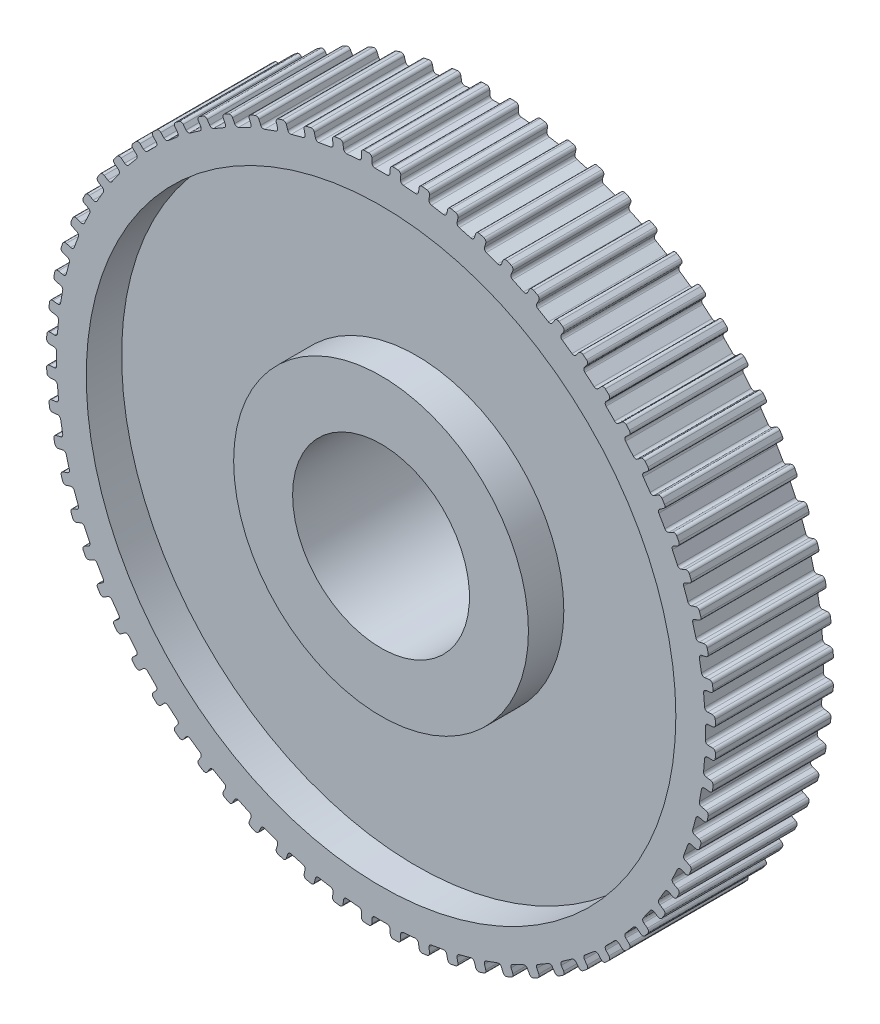
SolidWorks part; units mm, degrees
ref_plane "Front Plane" through (0, 0, 0) normal (0, 0, 1) x (1, 0, 0)
ref_plane "Top Plane" through (0, 0, 0) normal (0, 1, 0) x (1, 0, 0)
ref_plane "Right Plane" through (0, 0, 0) normal (1, 0, 0) x (0, 0, -1)
sketch "Sketch1" plane through (0, 0, 0) normal (0, 0, 1) x (1, 0, 0)
  circle A0 centre (0, 0) radius 56.75
  circle A1 centre (0, 0) radius 3.5
  dimension "D1" = 113.5
  dimension "D2" = 7
extrude "Boss-Extrude1" add sketch "Sketch1" along normal blind 20
ref_plane "Plane4" through (0, 0, 20) normal (0, 0, 1) x (1, 0, 0)
sketch "Sketch3" plane through (0, 0, 20) normal (0, 0, 1) x (1, 0, 0)
  circle A0 centre (0, 0) radius 25
  circle A3 centre (0, 0) radius 50
  dimension "D1" = 50
  dimension "D2" = 100
extrude "Cut-Extrude1" cut sketch "Sketch3" against normal blind 6
ref_plane "Plane5" through (0, 0, 10) normal (0, 0, 1) x (1, 0, 0)
mirror "Mirror1" about plane through (0, 0, 10) normal (0, 0, 1) of "Cut-Extrude1"
sketch "Sketch5" plane through (0, 0, 0) normal (0, 0, -1) x (-1, 0, 0)
  circle A1 centre (0, 0) radius 25 construction
  circle A2 centre (0, 0) radius 25
extrude "Boss-Extrude2" add sketch "Sketch5" along normal blind 10
sketch "Sketch6" plane through (0, 0, 0) normal (0, 0, -1) x (-1, 0, 0)
  line L0 (56.75, 0) -> (57.25, 0) construction
  line L1 (55, 1.5) -> (55, -1.5)
  line L2 (55, -1.5) -> (56.966, -1.6)
  line L3 (56.966, -1.6) -> (57, 0)
  line L4 (56.966, 1.6) -> (57, 0)
  line L5 (55, 1.5) -> (56.966, 1.6)
  circle A0 centre (0, 0) radius 56.75 construction
  point P12 (55, 0)
  dimension "D1" = 1.5
  dimension "D2" = 2
  dimension "D3" = 55
  dimension "D4" = 1.6
extrude "Cut-Extrude2" cut sketch "Sketch6" against normal through all
fillet "Fillet1" radius 0.5 2 edges at (-56.7278, -1.5879, 10) (-56.7278, 1.5879, 10)
fillet "Fillet3" radius 0.5 2 edges at (-55, -1.5, 10) (-55, 1.5, 10)
pattern_circular "CirPattern1" count 72 over 360 about axis through (0, 0, 0) along (0, 0, 1) of "Cut-Extrude2", "Fillet1", "Fillet3"
sketch "Sketch7" plane through (0, 0, 0) normal (0, 0, 1) x (1, 0, 0)
  circle A0 centre (0, 0) radius 3.5 construction
  circle A1 centre (0, 0) radius 3.5
extrude "Cut-Extrude3" cut sketch "Sketch7" against normal through all
sketch "Sketch8" plane through (0, 0, -10) normal (0, 0, -1) x (-1, 0, 0)
  circle A0 centre (0, 0) radius 15
  dimension "D1" = 30
extrude "Cut-Extrude4" cut sketch "Sketch8" against normal through all
